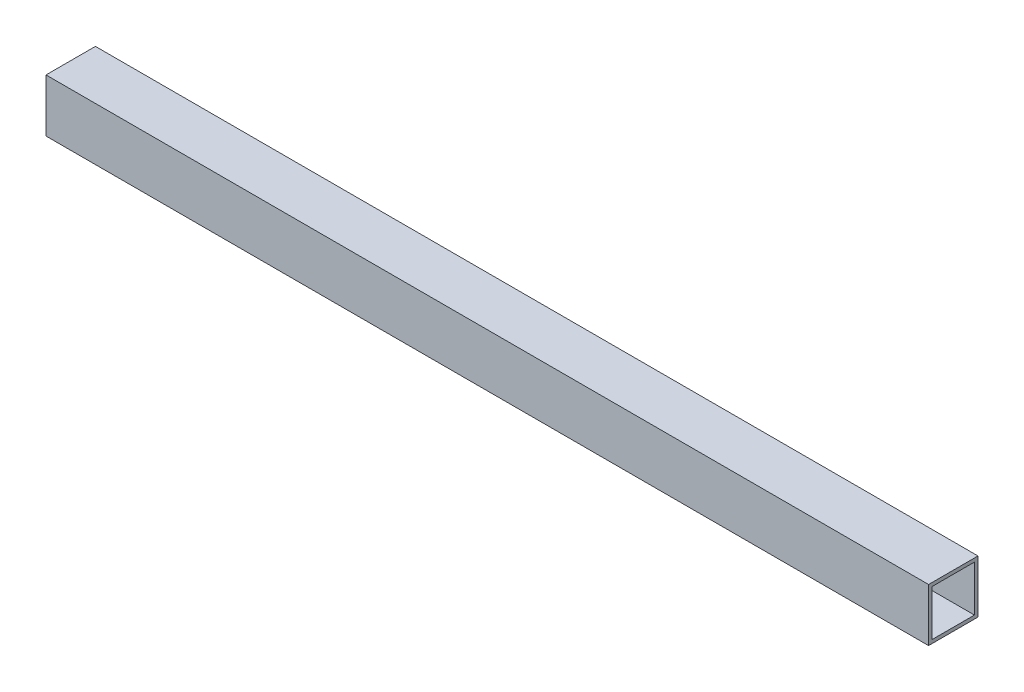
SolidWorks part; units mm, degrees
ref_plane "Спереди" through (0, 0, 0) normal (0, 0, 1) x (1, 0, 0)
ref_plane "Сверху" through (0, 0, 0) normal (0, 1, 0) x (1, 0, 0)
ref_plane "Справа" through (0, 0, 0) normal (1, 0, 0) x (0, 0, -1)
sketch "Эскиз2" plane through (0, 0, 0) normal (1, 0, 0) x (0, 0, -1)
  line L1 (-35, 37.5) -> (35, 37.5)
  line L2 (-35, 37.5) -> (-35, -37.5)
  line L3 (-35, -37.5) -> (35, -37.5)
  line L4 (35, 37.5) -> (35, -37.5)
  line L5 (-35, 37.5) -> (35, -37.5) construction
  line L6 (-35, -37.5) -> (35, 37.5) construction
  point P0 (0, 0)
extrude "Вытянуть-Тонкостенный1" add sketch "Эскиз2" along normal blind 1250 thin thin type one direction reverse wall 5
